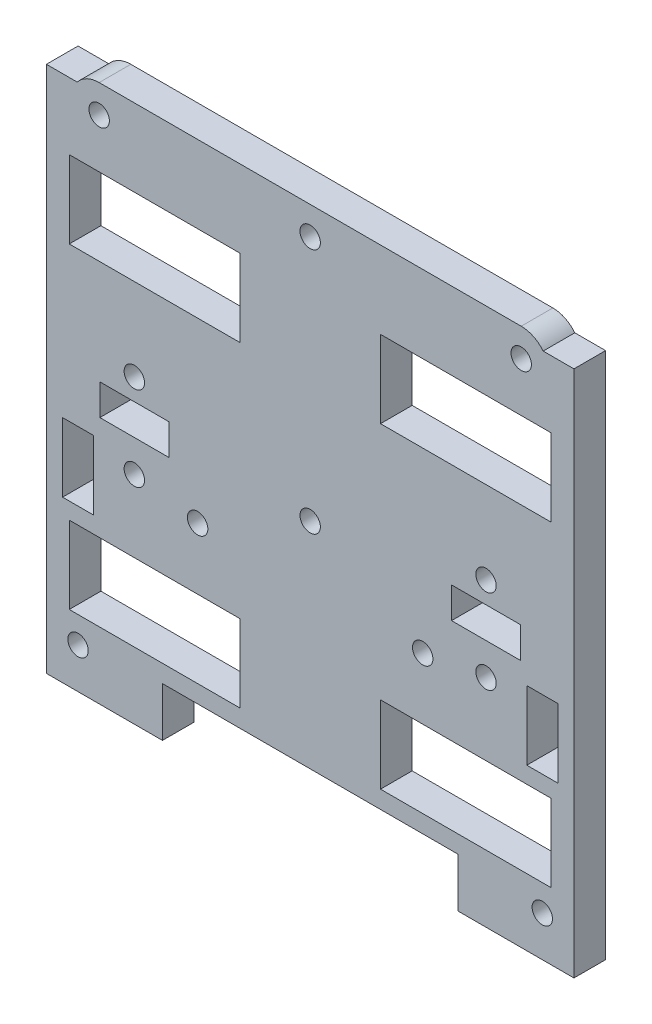
SolidWorks part; units mm, degrees
ref_plane "Front Plane" through (0, 0, 0) normal (0, 0, 1) x (1, 0, 0)
ref_plane "Top Plane" through (0, 0, 0) normal (0, 1, 0) x (1, 0, 0)
ref_plane "Right Plane" through (0, 0, 0) normal (1, 0, 0) x (0, 0, -1)
sketch "Sketch1" plane through (0, 0, 0) normal (0, 0, 1) x (1, 0, 0)
  line L0 (0, -37.5) -> (0, 37.5) construction
  line L1 (-47.5, -37.5) -> (47.5, -37.5)
  line L2 (-47.5, -37.5) -> (-47.5, 37.5)
  line L3 (-47.5, 37.5) -> (47.5, 37.5)
  line L4 (47.5, -37.5) -> (47.5, 37.5)
  line L5 (-47.5, -37.5) -> (47.5, 37.5) construction
  line L6 (-47.5, 37.5) -> (47.5, -37.5) construction
  line L7 (-47.5, 0) -> (47.5, 0) construction
  line L8 (-47.5, 22.5) -> (47.5, 22.5) construction
  line L9 (34.25, 17) -> (10, 28) construction
  line L10 (-34.25, 28) -> (-10, 28)
  line L11 (-34.25, 28) -> (-34.25, 17)
  line L12 (-34.25, 17) -> (-10, 17)
  line L13 (-10, 28) -> (-10, 17)
  line L14 (-34.25, 28) -> (-10, 17) construction
  line L15 (-34.25, 17) -> (-10, 28) construction
  line L16 (34.25, 28) -> (10, 17) construction
  line L17 (10, 28) -> (10, 17)
  line L18 (34.25, 17) -> (10, 17)
  line L19 (34.25, 28) -> (34.25, 17)
  line L20 (34.25, 28) -> (10, 28)
  line L21 (34.25, -28) -> (10, -17) construction
  line L22 (-34.25, -17) -> (-10, -28) construction
  line L23 (-34.25, -28) -> (-10, -17) construction
  line L24 (34.25, -17) -> (10, -28) construction
  line L25 (34.25, -28) -> (10, -28)
  line L26 (34.25, -28) -> (34.25, -17)
  line L27 (34.25, -17) -> (10, -17)
  line L28 (10, -28) -> (10, -17)
  line L29 (-10, -28) -> (-10, -17)
  line L30 (-34.25, -17) -> (-10, -17)
  line L31 (-34.25, -28) -> (-34.25, -17)
  line L32 (-34.25, -28) -> (-10, -28)
  point P0 (0, 0)
  point P12 (-22.125, 22.5)
  point P21 (22.125, 22.5)
  point P30 (22.125, -22.5)
  point P31 (-22.125, -22.5)
  dimension "D1" = 95
  dimension "D2" = 75
  dimension "D3" = 22.5
  dimension "D4" = 24.25
  dimension "D5" = 11
  dimension "D6" = 10
extrude "Boss-Extrude1" add sketch "Sketch1" along normal blind 4.5
sketch "Sketch8" plane through (0, 0, 4.5) normal (0, 0, 1) x (1, 0, 0)
  line L0 (-47.5, 37.5) -> (-47.5, -37.5) construction
  line L1 (47.5, -37.5) -> (47.5, 37.5) construction
  circle A0 centre (-47.5, 29.5) radius 8
  circle A1 centre (47.5, 29.5) radius 8
  dimension "D1" = 16
extrude "Boss-Extrude2" [suppressed] add sketch "Sketch8" against normal through all
sketch "Sketch2" plane through (0, 0, 4.5) normal (0, 0, 1) x (1, 0, 0)
  line L0 (0, -37.5) -> (0, 37.5) construction
  line L1 (-47.5, -37.5) -> (47.5, -37.5) construction
  line L2 (47.5, 37.5) -> (-47.5, 37.5) construction
  line L3 (-47.5, 0) -> (47.5, 0) construction
  line L4 (-47.5, 37.5) -> (-47.5, -37.5) construction
  line L5 (47.5, -37.5) -> (47.5, 37.5) construction
  line L6 (-40, 0) -> (40, 0) construction
  line L7 (-30, 35) -> (30, 35) construction
  circle A0 centre (-30, 35) radius 1.45
  circle A1 centre (30, 35) radius 1.45
  circle A2 centre (40, 0) radius 1.45
  circle A3 centre (-40, 0) radius 1.45
  circle A4 centre (0, 35) radius 1.45
  dimension "D1" = 2.9
  dimension "D7" = 2.9
  dimension "D8" = 2.9
  dimension "D9" = 2.9
  dimension "D2" = 30
  dimension "D3" = 35
  dimension "D4" = 80
  dimension "D5" = 40
  dimension "D6" = 0
extrude "screwHoles" cut sketch "Sketch2" against normal through all
sketch "Sketch3" plane through (0, 0, 4.5) normal (0, 0, 1) x (1, 0, 0)
  line L0 (-47.5, -20) -> (26.0486, -20) construction
  line L1 (-47.5, 37.5) -> (-47.5, -37.5) construction
  line L3 (0, 37.5) -> (0, -37.5) construction
  line L4 (47.5, 37.5) -> (-47.5, 37.5) construction
  line L5 (-47.5, -37.5) -> (47.5, -37.5) construction
  line L6 (18.95, -22.2) -> (9.05, -17.8) construction
  line L7 (-18.95, -17.8) -> (-9.05, -17.8)
  line L8 (-18.95, -17.8) -> (-18.95, -22.2)
  line L9 (-18.95, -22.2) -> (-9.05, -22.2)
  line L10 (-9.05, -17.8) -> (-9.05, -22.2)
  line L11 (-18.95, -17.8) -> (-9.05, -22.2) construction
  line L12 (-18.95, -22.2) -> (-9.05, -17.8) construction
  line L13 (18.95, -17.8) -> (9.05, -22.2) construction
  line L14 (9.05, -17.8) -> (9.05, -22.2)
  line L15 (18.95, -22.2) -> (9.05, -22.2)
  line L16 (18.95, -17.8) -> (18.95, -22.2)
  line L17 (18.95, -17.8) -> (9.05, -17.8)
  line L18 (-47.5, 37.5) -> (-47.5, -37.5) construction
  point P2 (-47.5, 0)
  point P12 (-14, -20)
  point P21 (14, -20)
  dimension "D1" = 9.9
  dimension "D2" = 4.4
  dimension "D3" = 14
  dimension "D4" = 20
extrude "BeltClamp" [suppressed] cut sketch "Sketch3" against normal through all
sketch "Sketch4" plane through (0, 0, 4.5) normal (0, 0, 1) x (1, 0, 0)
  line L0 (-47.5, 0) -> (47.5, 0) construction
  line L1 (-47.5, 37.5) -> (-47.5, -37.5) construction
  line L2 (47.5, -37.5) -> (47.5, 37.5) construction
  line L3 (0, 0) -> (0, 33.55) construction
  line L4 (-29.9, 2.2) -> (-20.1, 2.2)
  line L5 (-29.9, 2.2) -> (-29.9, -2.2)
  line L6 (-29.9, -2.2) -> (-20.1, -2.2)
  line L7 (-20.1, 2.2) -> (-20.1, -2.2)
  line L8 (-29.9, 2.2) -> (-20.1, -2.2) construction
  line L9 (-29.9, -2.2) -> (-20.1, 2.2) construction
  line L10 (29.9, -2.2) -> (20.1, 2.2) construction
  line L11 (29.9, 2.2) -> (20.1, -2.2) construction
  line L12 (20.1, 2.2) -> (20.1, -2.2)
  line L13 (29.9, -2.2) -> (20.1, -2.2)
  line L14 (29.9, 2.2) -> (29.9, -2.2)
  line L15 (29.9, 2.2) -> (20.1, 2.2)
  line L16 (-29.9, -2.2) -> (-20.1, 2.2) construction
  circle A0 centre (-40, 0) radius 1.45 construction
  circle A1 centre (0, 35) radius 1.45 construction
  circle A2 centre (0, 0) radius 1.45
  point P6 (-25, 0)
  point P22 (25, 0)
  dimension "D2" = 4.4
  dimension "D5" = 2.9
  dimension "D3" = 0
  dimension "D4" = 25
extrude "Cut-Extrude3" cut sketch "Sketch4" against normal through all
sketch "Sketch5" plane through (0, 0, 4.5) normal (0, 0, 1) x (1, 0, 0)
  line L0 (-47.5, -9.75) -> (47.5, -9.75) construction
  line L1 (-47.5, 37.5) -> (-47.5, -37.5) construction
  line L2 (47.5, -37.5) -> (47.5, 37.5) construction
  line L4 (0, -37.5) -> (0, 37.5) construction
  line L5 (-47.5, -37.5) -> (47.5, -37.5) construction
  line L6 (47.5, 37.5) -> (-47.5, 37.5) construction
  line L7 (-30.8, -14.65) -> (-35.2, -4.85) construction
  line L8 (30.8, -4.85) -> (35.2, -4.85)
  line L9 (30.8, -4.85) -> (30.8, -14.65)
  line L10 (30.8, -14.65) -> (35.2, -14.65)
  line L11 (35.2, -4.85) -> (35.2, -14.65)
  line L12 (30.8, -4.85) -> (35.2, -14.65) construction
  line L13 (30.8, -14.65) -> (35.2, -4.85) construction
  line L14 (-30.8, -4.85) -> (-35.2, -14.65) construction
  line L15 (-35.2, -4.85) -> (-35.2, -14.65)
  line L16 (-30.8, -14.65) -> (-35.2, -14.65)
  line L17 (-30.8, -4.85) -> (-30.8, -14.65)
  line L18 (-30.8, -4.85) -> (-35.2, -4.85)
  line L19 (33, -9.75) -> (33, -37.5) construction
  line L20 (-33, -9.75) -> (-33, -37.5) construction
  line L21 (-33, -31.75) -> (33, -31.75) construction
  circle A0 centre (33, -31.75) radius 1.45
  circle A1 centre (-33, -31.75) radius 1.45
  point P15 (33, -9.75)
  point P24 (-33, -9.75)
  dimension "D5" = 2.9
  dimension "D2" = 9.8
  dimension "D3" = 4.4
  dimension "D4" = 33
  dimension "D6" = 22
  dimension "D1" = 9.75
extrude "Cut-Extrude4" cut sketch "Sketch5" against normal through all
sketch "Sketch9" plane through (0, 0, 4.5) normal (0, 0, 1) x (1, 0, 0)
  line L0 (47.5, 37.5) -> (-47.5, 37.5) construction
  line L1 (0, 37.5) -> (0, -37.5) construction
  line L2 (-47.5, -37.5) -> (47.5, -37.5) construction
  line L3 (50.5, 35) -> (45.5, 35) construction
  line L4 (-50.5, 35) -> (-45.5, 35) construction
  circle A0 centre (-30, 35) radius 4
  circle A1 centre (-30, 35) radius 1.45
  circle A2 centre (-30, 35) radius 1.45 construction
  circle A3 centre (30, 35) radius 1.45
  circle A4 centre (30, 35) radius 4
  point P17 (0, -37.5)
  dimension "D1" = 8
extrude "Boss-Extrude3" add sketch "Sketch9" against normal through all
sketch "Sketch10" plane through (0, 0, 4.5) normal (0, 0, 1) x (1, 0, 0)
  line L0 (-60, 37.5) -> (-37.5, 37.5)
  line L1 (-37.5, 37.5) -> (-37.5, -37.5)
  line L2 (-47.5, -37.5) -> (47.5, -37.5) construction
  line L3 (-37.5, -37.5) -> (-60, -37.5)
  line L4 (-60, -37.5) -> (-60, 37.5)
  line L5 (0, 37.5) -> (0, -37.5) construction
  line L6 (26.8775, 37.5) -> (-26.8775, 37.5) construction
  line L7 (60, -37.5) -> (60, 37.5)
  line L8 (37.5, -37.5) -> (60, -37.5)
  line L9 (37.5, 37.5) -> (37.5, -37.5)
  line L10 (60, 37.5) -> (37.5, 37.5)
  line L11 (-60, -37.5) -> (-60, 37.5)
  line L12 (-33.1225, 37.5) -> (-47.5, 37.5) construction
  line M3 (47.5, -37.5) -> (47.5, 37.5)
  line M7 (-47.5, 37.5) -> (-47.5, -37.5)
  line M8 (-47.5, -37.5) -> (47.5, -37.5)
  dimension "D3" = 0
  dimension "D1" = 75
  dimension "D2" = 60
extrude "Cut-Extrude5" cut sketch "Sketch10" against normal through all contours L1 L0 M7 M8 | L10 L9 M3 M8 region at (42.5, 0, 4.5) region at (-42.5, 0, 4.5)
sketch "Sketch11" plane through (0, 0, 4.5) normal (0, 0, 1) x (1, 0, 0)
  line L0 (-30, 39) -> (30, 39)
  line L1 (30, 39) -> (26.8775, 37.5)
  line L2 (26.8775, 37.5) -> (-26.8775, 37.5)
  line L3 (-26.8775, 37.5) -> (-30, 39)
  arc A0 (-26.8775, 37.5) -> (-33.1225, 37.5) centre (-30, 35) ccw construction
  arc A1 (33.1225, 37.5) -> (26.8775, 37.5) centre (30, 35) ccw construction
extrude "Boss-Extrude4" add sketch "Sketch11" against normal through all
sketch "Sketch12" plane through (0, 0, 4.5) normal (0, 0, 1) x (1, 0, 0)
  line L0 (-37.5, -8.25) -> (37.5, -8.25) construction
  line L1 (-37.5, 37.5) -> (-37.5, -37.5) construction
  line L2 (37.5, 37.5) -> (37.5, -37.5) construction
  line L3 (0, 0) -> (0, -37.5) construction
  line L4 (-37.5, -37.5) -> (37.5, -37.5) construction
  circle A0 centre (-16, -8.25) radius 1.45
  circle A1 centre (16, -8.25) radius 1.45
  dimension "D2" = 2.9
  dimension "D1" = 16
  dimension "D3" = 8.25
extrude "FanBraceScrews" cut sketch "Sketch12" against normal through all
sketch "Sketch13" plane through (0, 0, 4.5) normal (0, 0, 1) x (1, 0, 0)
  line L0 (-37.5, -37.5) -> (37.5, -37.5) construction
  line L1 (-21, -44.5) -> (21, -44.5)
  line L2 (-21, -44.5) -> (-21, -30.5)
  line L3 (-21, -30.5) -> (21, -30.5)
  line L4 (21, -44.5) -> (21, -30.5)
  line L5 (-21, -44.5) -> (21, -30.5) construction
  line L6 (-21, -30.5) -> (21, -44.5) construction
  point P0 (0, -37.5)
  dimension "D1" = 42
  dimension "D2" = 7
extrude "Cut-Extrude7" cut sketch "Sketch13" against normal through all
sketch "Sketch14" plane through (0, 0, 4.5) normal (0, 0, 1) x (1, 0, 0)
  line L0 (16, -9.7) -> (16, 3.75) construction
  line L1 (0, 0) -> (0, -40.3958) construction
  line L2 (-16, -9.7) -> (-16, 3.75) construction
  circle A0 centre (16, -8.25) radius 1.45 construction
  circle A1 centre (16, 3.75) radius 1.45
  circle A2 centre (-16, 3.75) radius 1.45
  dimension "D2" = 2.9
  dimension "D1" = 12
extrude "Cut-Extrude8" [suppressed] cut sketch "Sketch14" against normal through all
sketch "Sketch15" plane through (0, 0, 4.5) normal (0, 0, 1) x (1, 0, 0)
  line L0 (-25, 5.25) -> (-25, -6.75) construction
  line L2 (0, 0) -> (0, -11.0705) construction
  line L3 (16, -8.3509) -> (25, -6.75) construction
  line L4 (25, 5.25) -> (25, -6.75) construction
  circle A0 centre (-25, 5.25) radius 1.45
  circle A1 centre (-25, -6.75) radius 1.45
  circle A2 centre (25, -6.75) radius 1.45
  circle A3 centre (25, 5.25) radius 1.45
  circle A5 centre (-16, -8.25) radius 1.45 construction
  dimension "D1" = 12
  dimension "D3" = 2.9
  dimension "D4" = 2.9
  dimension "D2" = 25
  dimension "D5" = 1.5
extrude "BeltClipScrews" cut sketch "Sketch15" against normal through all
sketch "Sketch16" [suppressed] plane through (0, 0, 4.5) normal (0, 0, 1) x (1, 0, 0)
  line L0 (0, 0) -> (0, -11.3016) construction
  line L1 (-30.1, 2.35) -> (-19.9, 2.35)
  line L2 (-30.1, 2.35) -> (-30.1, -2.35)
  line L3 (-30.1, -2.35) -> (-19.9, -2.35)
  line L4 (-19.9, 2.35) -> (-19.9, -2.35)
  line L5 (-35.35, -4.65) -> (-30.65, -4.65)
  line L6 (-35.35, -4.65) -> (-35.35, -14.85)
  line L7 (-35.35, -14.85) -> (-30.65, -14.85)
  line L8 (-30.65, -4.65) -> (-30.65, -14.85)
  line L9 (30.65, -4.65) -> (30.65, -14.85)
  line L10 (35.35, -14.85) -> (30.65, -14.85)
  line L11 (35.35, -4.65) -> (35.35, -14.85)
  line L12 (35.35, -4.65) -> (30.65, -4.65)
  line L13 (19.9, 2.35) -> (19.9, -2.35)
  line L14 (30.1, -2.35) -> (19.9, -2.35)
  line L15 (30.1, 2.35) -> (30.1, -2.35)
  line L16 (30.1, 2.35) -> (19.9, 2.35)
  line L17 (-30.65, -4.65) -> (-30.65, -14.85)
extrude "Boss-Extrude5" [suppressed] add sketch "Sketch16" against normal through all contours L8 L5 L6 L7 | L4 L1 L2 L3 | L15 L16 L13 L14 | L11 L12 L9 L10
equation "\"X-ROD-SPACING\"=45"
equation "\"Y-ROD-SPACING\"=75"
equation "\"Z-ROD-SPACING\"=17.5"
equation "\"Y-BED-OFFSET\"=2"
equation "\"Y-BED-ROD-INSET\"=3.5"
equation "\"Y-BED-SCREW-SPACING\"=209"
equation "\"Y-BED-SCREW-CUTOUT-SLOT-HEIGHT\"=2"
equation "\"T-SLOT-NUT-FILLET-RADIUS\"=0.5"
equation "\"T-SLOT-SCREW-SHAFT-RADIUS\"=1.55"
equation "\"T-SLOT-SCREW-SHAFT-CUTOUT-LENGTH\"=11.0"
equation "\"T-SLOT-NUT-DEPTH\"=3.5"
equation "\"T-SLOT-NUT-WIDTH\"=2.85"
equation "\"T-SLOT-NUT-END-DISTANCE\"=8"
equation "\"ACRYLIC-THICKNESS\"=10"
equation "\"ACRYLIC-THICKNESS2\"=4.5"
equation "\"ACRYLIC-TAB-CUTOUT-SIZE\"=\"ACRYLIC-THICKNESS\"+\"ACRYLIC-TAB-TOLERANCE\"*2"
equation "\"ACRYLIC-TAB-WIDTH\"=\"ACRYLIC-THICKNESS\""
equation "\"ACRYLIC-M3-HOLE\"=2.9"
equation "\"SMOOTHROD-CAP-SCREW-DISTANCE\"=20"
equation "\"FRAME-WIDTH-INNER\"=370"
equation "\"NEMA17-HOLE-SPACING\"=31"
equation "\"NEMA17-CENTRAL-CUTOUT\"=22.5"
equation "\"Z-BRACKET-REACH\"=55"
equation "\"Z-ROD-INSET\"=16"
equation "\"TOP-BRACKET-SPACING\"=40"
equation "\"SMOOTHROD-X-LENGTH\"=350"
equation "\"SMOOTHROD-Y-LENGTH\"=350"
equation "\"SMOOTHROD-Z-LENGTH\"=350"
equation "\"SMOOTHROD-TIGHTENING-HEADROOM\"=.25"
equation "\"LEADSCREW-Z-LENGTH\"=300"
equation "\"SCREW-LENGTH-FRAME\"=\"ACRYLIC-THICKNESS\" + 10"
equation "\"SCREW-LENGTH-MOTOR\"=\"ACRYLIC-THICKNESS\" + 5"
equation "\"SCREW-HEAD-RADIUS\"=6"
equation "\"PRINTED-X-SMOOTHROD-DIAMETER\"=8.4"
equation "\"PRINTED-X-SMOOTHROD-CUTOUT\"=10"
equation "\"PRINTED-X-BASE-HEIGHT\"=10"
equation "\"PRINTED-LM8UU-CUTOUT-SIZE\"=15.5"
equation "\"PRINTED-LM8UU-CUTOUT-LENGTH\"=24.5"
equation "\"PRINTED-X-IDLER-HEIGHT\"=16"
equation "\"PSU-MOUNTING-WIDTH\"=95"
equation "\"PSU-MOUNTING-HEIGHT\"=177"
equation "\"Y-BELT-TO-ROD-DISTANCE\"=20"
equation "\"SPOOL-HOLDER-ROD-SPACING\"=150"
equation "\"D3@Sketch1\"=\"X-ROD-SPACING\"/2"
equation "\"D4@Sketch1\"=\"ACRYLIC-X-CARRIAGE-LM8UU-CUTOUT-WIDTH\""
equation "\"D1@Boss-Extrude1\"=\"ACRYLIC-THICKNESS2\""
equation "\"D1@Sketch2\"=\"ACRYLIC-M3-HOLE\""
equation "\"D1@Sketch3\"=\"ACRYLIC-TAB-CUTOUT-SIZE\""
equation "\"D2@Sketch3\"=\"ACRYLIC-THICKNESS2\"+\"ACRYLIC-TAB-TOLERANCE\"*2"
equation "\"ACRYLIC-X-CARRIAGE-WIDTH\"=55"
equation "\"ACRYLIC-X-CARRIAGE-HEIGHT\"=75"
equation "\"D2@Sketch1\"=\"ACRYLIC-X-CARRIAGE-HEIGHT\""
equation "\"ACRYLIC-X-CARRIAGE-CENTER-TAB-SPACING\"=14"
equation "\"D3@Sketch3\"=\"ACRYLIC-X-CARRIAGE-CENTER-TAB-SPACING\""
equation "\"SCREW-LENGTH-EXTRUDER\"=28"
equation "\"ACRYLIC-X-CARRIAGE-SCREW-SPACING-X\"=15"
equation "\"ACRYLIC-X-CARRIAGE-SCREW-SPACING-Y\"=33"
equation "\"D1@Sketch4\"=\"ACRYLIC-THICKNESS2-TAB-CUTOUT-HEIGHT\""
equation "\"D2@Sketch4\"=\"ACRYLIC-THICKNESS2-TAB-CUTOUT-WIDTH\""
equation "\"D2@Sketch5\"=\"ACRYLIC-THICKNESS2-TAB-CUTOUT-HEIGHT\""
equation "\"D3@Sketch5\"=\"ACRYLIC-THICKNESS2-TAB-CUTOUT-WIDTH\""
equation "\"ACRYLIC-X-CARRIAGE-EXTRUDER-SHELF-DEPTH\"=\"ACRYLIC-X-CARRIAGE-EXTRUDER-OFFSET\" + 28"
equation "\"ACRYLIC-X-CARRIAGE-EXTRUDER-BRACE-SPACING\"=23"
equation "\"D4@Sketch5\"=\"ACRYLIC-X-CARRIAGE-DUAL-MOUNT-BRACE-WIDTH\""
equation "\"D1@Sketch5\"=\"ACRYLIC-THICKNESS2\"/2 + 7.5"
equation "\"D4@Sketch2\"=\"ACRYLIC-X-CARRIAGE-DUAL-MOUNT-SCREW-WIDTH\"*2"
equation "\"D5@Sketch2\"=\"ACRYLIC-X-CARRIAGE-DUAL-MOUNT-SCREW-WIDTH\""
equation "\"D7@Sketch2\"=\"ACRYLIC-M3-HOLE\""
equation "\"D8@Sketch2\"=\"ACRYLIC-M3-HOLE\""
equation "\"ACRYLIC-X-CARRIAGE-LM8UU-CUTOUT-WIDTH\"=24.25"
equation "\"ACRYLIC-TAB-TOLERANCE\"=-.05"
equation "\"ACRYLIC-X-CARRIAGE-EXTRUDER-OFFSET\"=26"
equation "\"ACRYLIC-X-CARRIAGE-EXTRUDER-ANGLE\"=90"
equation "\"ACRYLIC-X-CARRIAGE-EXTRUDER-BRACE-TAB-OFFSET\"=20"
equation "\"ACRYLIC-X-CARRIAGE-EXTRUDER-BRACE-HEIGHT\"=35"
equation "\"ACRYLIC-X-CARRIAGE-EXTRUDER-BRACE-SCREW-SPACING\"=22"
equation "\"D5@Sketch5\"=\"ACRYLIC-M3-HOLE\""
equation "\"ACRYLIC-X-CARRIAGE-DUAL-WIDTH-MULTIPLIER\"=1.65"
equation "\"ACRYLIC-X-CARRIAGE-DUAL-HOTEND-SPACING\"=42"
equation "\"ACRYLIC-X-CARRIAGE-DUAL-WIDTH\"=75"
equation "\"ACRYLIC-X-CARRIAGE-DUAL-HOTEND-SEPARATION\"=36"
equation "\"ACRYLIC-X-CARRIAGE-DUAL-MOUNT-PLATE-DEPTH\"=75"
equation "\"ACRYLIC-X-CARRIAGE-DUAL-MOUNT-BRACE-WIDTH\"=33"
equation "\"ACRYLIC-X-CARRIAGE-DUAL-MOUNT-SCREW-WIDTH\"=40"
equation "\"D9@Sketch2\"=\"ACRYLIC-M3-HOLE\""
equation "\"ACRYLIC-X-CARRIAGE-LM8UU-CUTOUT-HEIGHT\"=11.0"
equation "\"D5@Sketch1\"=\"ACRYLIC-X-CARRIAGE-LM8UU-CUTOUT-HEIGHT\""
equation "\"D1@Sketch10\"=\"ACRYLIC-X-CARRIAGE-DUAL-WIDTH\""
equation "\"D5@Sketch4\"=\"ACRYLIC-M3-HOLE\""
equation "\"D2@Sketch12\"=\"ACRYLIC-M3-HOLE\""
equation "\"D3@Sketch12\"=\"ACRYLIC-THICKNESS2\"/2 + 6"
equation "\"D2@Sketch14\"=\"ACRYLIC-M3-HOLE\""
equation "\"D3@Sketch15\"=\"ACRYLIC-M3-HOLE\""
equation "\"D4@Sketch15\"=\"ACRYLIC-M3-HOLE\""
equation "\"KERF\"=0.05"
equation "\"ACRYLIC-THICKNESS-TAB-CUTOUT-WIDTH\"=\"ACRYLIC-THICKNESS\"-\"KERF\"*2"
equation "\"ACRYLIC-THICKNESS-TAB-CUTOUT-HEIGHT\"=\"ACRYLIC-TAB-WIDTH\"-\"KERF\"*4"
equation "\"ACRYLIC-THICKNESS2-TAB-CUTOUT-WIDTH\"=\"ACRYLIC-THICKNESS2\"-\"KERF\"*2"
equation "\"ACRYLIC-THICKNESS2-TAB-CUTOUT-HEIGHT\"=\"ACRYLIC-TAB-WIDTH\"-\"KERF\"*4"
equation "\"PRINTED-M3-HOLE\"=3.5"
equation "\"PRINTED-M3-NUT-AF\"=6.25"
equation "\"ACRYLIC-X-CARRIAGE-DUAL-FAN-OFFSET\"=52"
equation "\"ACRYLIC-X-CARRIAGE-DUAL-FAN-HEIGHT\"=20"
equation "\"BLOWER-FAN-WIDTH\"=15"
